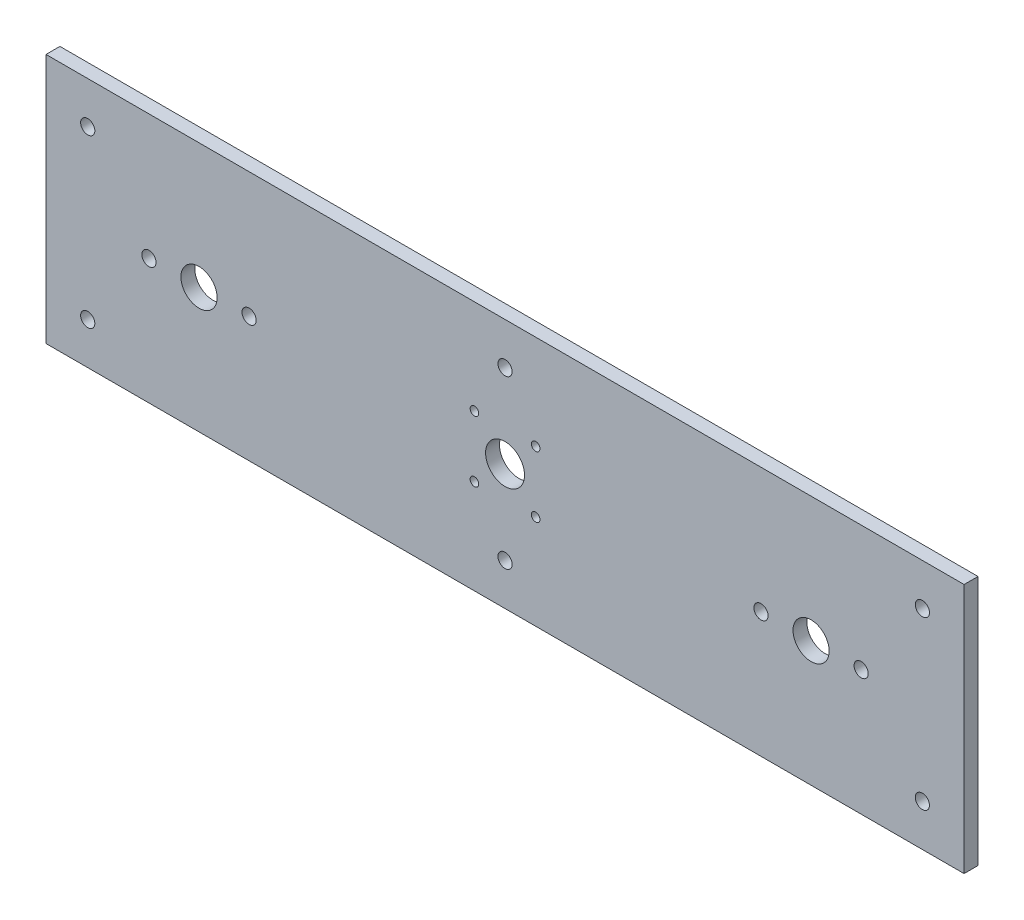
SolidWorks part; units mm, degrees
ref_plane "Front Plane" through (0, 0, 0) normal (0, 0, 1) x (1, 0, 0)
ref_plane "Top Plane" through (0, 0, 0) normal (0, 1, 0) x (1, 0, 0)
ref_plane "Right Plane" through (0, 0, 0) normal (1, 0, 0) x (0, 0, -1)
sketch "Sketch1" plane through (0, 0, 0) normal (0, 0, 1) x (1, 0, 0)
  line L1 (-165, -45) -> (165, -45)
  line L2 (-165, -45) -> (-165, 45)
  line L3 (-165, 45) -> (165, 45)
  line L4 (165, -45) -> (165, 45)
  line L5 (-165, -45) -> (165, 45) construction
  line L6 (-165, 45) -> (165, -45) construction
  point P0 (0, 0)
  dimension "D1" = 330
  dimension "D2" = 90
extrude "Boss-Extrude1" add sketch "Sketch1" along normal mid plane 5
sketch "Sketch2" plane through (0, 0, 2.5) normal (0, 0, 1) x (1, 0, 0)
  line L3 (165, 30) -> (-165, 30)
  line L4 (165, 30) -> (-165, 30) construction
  line L6 (-150, 45) -> (-150, -45)
  line L7 (-150, 45) -> (-150, -45) construction
  line L9 (-165, -30) -> (165, -30)
  line L10 (-165, -30) -> (165, -30) construction
  line L11 (0, 45) -> (0, -45) construction
  line L12 (150, -45) -> (150, 45)
  line L13 (150, -45) -> (150, 45) construction
  line L14 (165, 45) -> (-165, 45) construction
  line L15 (-165, -45) -> (165, -45) construction
  circle A0 centre (150, 30) radius 2.55
  circle A1 centre (150, -30) radius 2.55
  circle A2 centre (0, 30) radius 2.55
  circle A3 centre (0, -30) radius 2.55
  circle A4 centre (-150, -30) radius 2.55
  circle A5 centre (-150, 30) radius 2.55
  dimension "D5" = 5.1
  dimension "D6" = 5.1
  dimension "D7" = 5.1
  dimension "D8" = 5.1
  dimension "D9" = 5.1
  dimension "D10" = 5.1
  dimension "D1" = 15
  dimension "D2" = 15
  dimension "D3" = 15
  dimension "D4" = 15
extrude "Cut-Extrude1" cut sketch "Sketch2" against normal through all
sketch "Sketch3" plane through (0, 0, 2.5) normal (0, 0, 1) x (1, 0, 0)
  line L0 (-165, 0) -> (165, 0) construction
  line L1 (-165, 45) -> (-165, -45) construction
  line L2 (165, -45) -> (165, 45) construction
  circle A0 centre (-110, 0) radius 6.5
  circle A1 centre (-92, 0) radius 2.55
  circle A2 centre (-128, 0) radius 2.55
  dimension "D1" = 13
  dimension "D2" = 5.1
  dimension "D4" = 5.1
  dimension "D3" = 110
  dimension "D5" = 18
  dimension "D6" = 18
extrude "Cut-Extrude2" cut sketch "Sketch3" against normal through all
mirror "Mirror1" about plane through (0, 0, 0) normal (1, 0, 0) of "Cut-Extrude2"
sketch "Sketch4" plane through (0, 0, 2.5) normal (0, 0, 1) x (1, 0, 0)
  line L1 (-11, -11) -> (11, -11) construction
  line L2 (-11, -11) -> (-11, 11) construction
  line L3 (-11, 11) -> (11, 11) construction
  line L4 (11, -11) -> (11, 11) construction
  line L5 (-11, -11) -> (11, 11) construction
  line L6 (-11, 11) -> (11, -11) construction
  circle A0 centre (11, 11) radius 1.55
  circle A1 centre (11, -11) radius 1.55
  circle A2 centre (-11, -11) radius 1.55
  circle A3 centre (-11, 11) radius 1.55
  circle A4 centre (0, 0) radius 7
  point P0 (0, 0)
  dimension "D3" = 3.1
  dimension "D4" = 3.1
  dimension "D5" = 3.1
  dimension "D6" = 3.1
  dimension "D7" = 14
  dimension "D1" = 22
  dimension "D2" = 22
extrude "Cut-Extrude3" cut sketch "Sketch4" against normal through all
